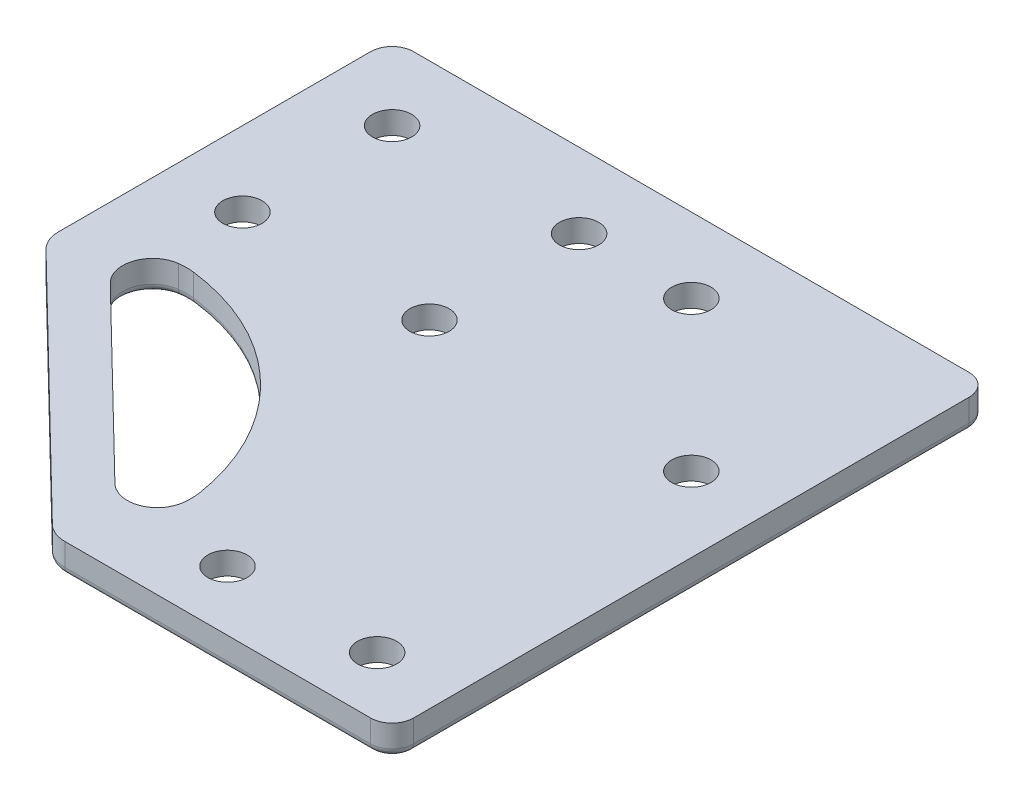
SolidWorks part; units mm, degrees
ref_plane "Front Plane" through (0, 0, 0) normal (0, 0, 1) x (1, 0, 0)
ref_plane "Top Plane" through (0, 0, 0) normal (0, 1, 0) x (1, 0, 0)
ref_plane "Right Plane" through (0, 0, 0) normal (1, 0, 0) x (0, 0, -1)
sketch "Sketch1" plane through (0, 0, 0) normal (0, 1, 0) x (1, 0, 0)
  line L0 (-70, -10) -> (-45, -10) construction
  line L1 (-2.8633, 0) -> (-77.1367, 0)
  line L2 (0, -2.8633) -> (0, -77.1367)
  line L3 (-2.8633, -80) -> (-36.2225, -80)
  line L4 (-80, -2.8633) -> (-80, -37.1367)
  line L5 (-70, -30) -> (-45, -30) construction
  line L6 (-10, -30) -> (-10, -72) construction
  line L7 (-30, -10) -> (-30, -72) construction
  line L8 (-73.987, -40) -> (-40, -40)
  line L9 (-40, -40) -> (-40, -73.1892)
  line L10 (-80, -37.1367) -> (-80, -46.2907)
  line L11 (-80, -46.2907) -> (-45.3765, -80)
  line L12 (-45.3765, -80) -> (-36.2225, -80)
  line L13 (-73.987, -40) -> (-73.987, -43.7709)
  line L14 (-73.987, -43.7709) -> (-43.7709, -73.1892)
  line L15 (-43.7709, -73.1892) -> (-40, -73.1892)
  circle A0 centre (-70, -10) radius 2.625
  circle A1 centre (-45, -10) radius 2.625
  circle A2 centre (-45, -30) radius 2.625
  circle A3 centre (-70, -30) radius 2.625
  circle A4 centre (-30, -10) radius 2.625
  circle A5 centre (-10, -30) radius 2.625
  circle A6 centre (-10, -72) radius 2.625
  circle A7 centre (-30, -72) radius 2.625
  arc A9 (-2.8633, -80) -> (0, -77.1367) centre (-2.8633, -77.1367) ccw
  arc A10 (0, -2.8633) -> (-2.8633, 0) centre (-2.8633, -2.8633) ccw
  arc A11 (-77.1367, 0) -> (-80, -2.8633) centre (-77.1367, -2.8633) ccw
  point P24 (-40, -80)
  point P29 (0, -80)
  point P32 (0, 0)
  point P35 (-80, 0)
  dimension "D2" = 5.25
  dimension "D16" = 6
  dimension "D3" = 10
  dimension "D4" = 20
  dimension "D5" = 10
  dimension "D6" = 20
  dimension "D7" = 8
  dimension "D8" = 10
  dimension "D9" = 50
  dimension "D10" = 35
  dimension "D11" = 80
  dimension "D12" = 80
  dimension "D13" = 15
  dimension "D14" = 40
  dimension "D15" = 8
  dimension "D18" = 40
extrude "Boss-Extrude1" add sketch "Sketch1" along normal blind 4
fillet "Fillet1" radius 30 1 edges at (-40, 2, 40)
sketch "Sketch2" plane through (0, 0, 0) normal (0, -1, 0) x (1, 0, 0)
  circle A0 centre (-10, 30) radius 5.05
  circle A1 centre (-30, 10) radius 5.05
  circle A2 centre (-45, 10) radius 5.05
  circle A3 centre (-70, 10) radius 5.05
  circle A4 centre (-70, 30) radius 5.05
  circle A5 centre (-45, 30) radius 5.05
  circle A6 centre (-30, 72) radius 5.05
  circle A7 centre (-10, 72) radius 5.05
  circle A8 centre (-45, 30) radius 2.625 construction
  dimension "D1" = 10.1
extrude "Cut-Extrude1" cut sketch "Sketch2" against normal blind 1
fillet "Fillet2" radius 1 7 edges at (-0.8386, 0, 0.8386) (0, 0, 40) (-0.8386, 0, 79.1614) (-24.1199, 0, 80) (-80, 0, 24.577) (-79.1614, 0, 0.8386) (-40, 0, 0)
fillet "Fillet3" [suppressed] radius 1
fillet "Fillet4" radius 8 2 edges at (-40, 2, 73.1892) (-73.987, 2, 40)
fillet "Fillet5" radius 4 2 edges at (-73.987, 2, 43.7709) (-43.7709, 2, 73.1892)
fillet "Fillet6" radius 1 6 edges at (-40.2693, 0, 66.4653) (-42.9881, 0, 70.8675) (-58.8481, 0, 58.5101) (-71.608, 0, 42.9331) (-67.3232, 0, 40.166) (-49.1448, 0, 48.4347)
fillet "Fillet8" radius 4 2 edges at (-45.3765, 2.5, 80) (-80, 2.5, 46.2907) tangent propagation no
fillet "Fillet9" radius 1 3 edges at (-78.8973, 0, 47.3603) (-46.4698, 0, 78.9339) (-62.6658, 0, 63.1672)
